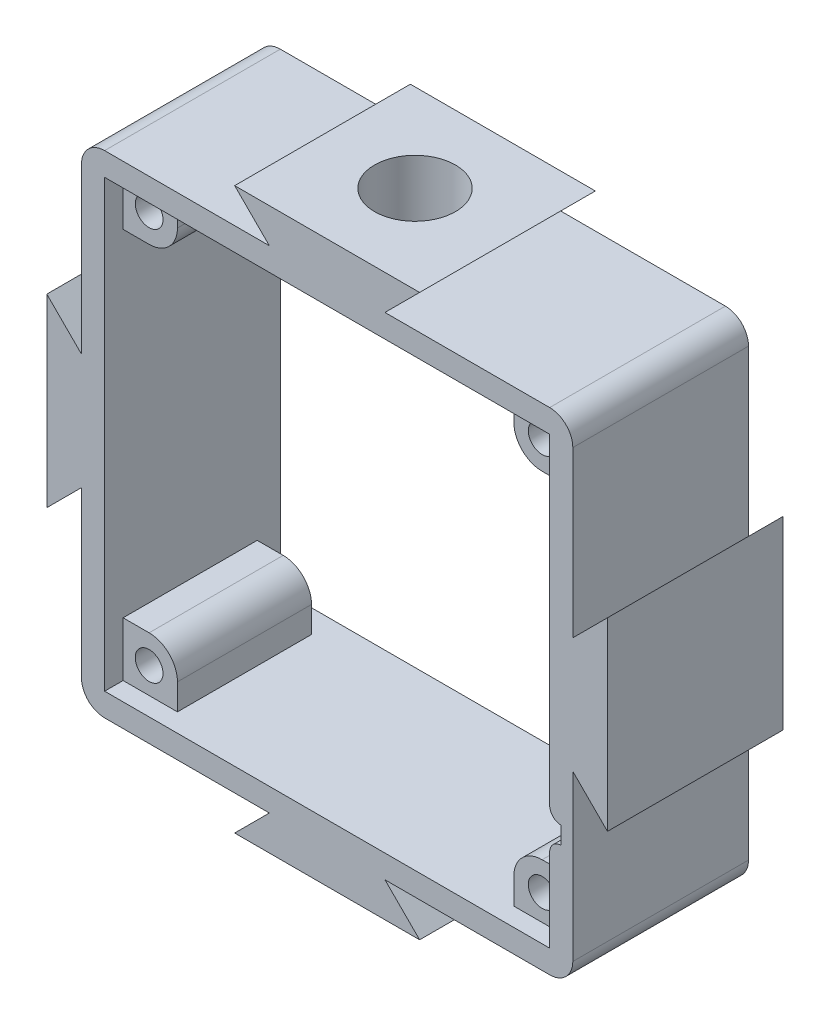
SolidWorks part; units mm, degrees
ref_plane "Front Plane" through (0, 0, 0) normal (0, 0, 1) x (1, 0, 0)
ref_plane "Top Plane" through (0, 0, 0) normal (0, 1, 0) x (1, 0, 0)
ref_plane "Right Plane" through (0, 0, 0) normal (1, 0, 0) x (0, 0, -1)
sketch "Sketch1" plane through (0, 0, 0) normal (0, 0, 1) x (1, 0, 0)
  line L0 (19.05, -19.05) -> (19.05, 19.05) construction
  line L5 (21.25, 21.25) -> (-21.25, 21.25)
  line L6 (-21.25, 21.25) -> (-21.25, -21.25)
  line L7 (-19.05, -19.05) -> (19.05, -19.05) construction
  line L8 (-19.05, 19.05) -> (-19.05, -19.05) construction
  line L9 (19.05, 19.05) -> (-19.05, 19.05) construction
  line L10 (19.05, -19.05) -> (19.05, 19.05) construction
  line L11 (-19.05, -19.05) -> (19.05, -19.05) construction
  line L12 (-19.05, 19.05) -> (-19.05, -19.05) construction
  line L13 (19.05, 19.05) -> (-19.05, 19.05) construction
  line L14 (19.25, -19.25) -> (19.25, 19.25)
  line L15 (19.25, 19.25) -> (-19.25, 19.25)
  line L16 (-19.25, 19.25) -> (-19.25, -19.25)
  line L17 (-19.25, -19.25) -> (19.25, -19.25)
  line L18 (-21.25, -21.25) -> (21.25, -21.25)
  line L19 (21.25, -21.25) -> (21.25, 21.25)
  point P17 (0, 0)
  point P18 (-25.4656, 13.9402)
  dimension "D2" = 2
  dimension "D1" = 0.2
extrude "Boss-Extrude2" add sketch "Sketch1" against normal up to surface (15.2 mm away)
sketch "Sketch2" plane through (0, 0, -1.6) normal (0, 0, -1) x (-1, 0, 0)
  line L0 (17, -14.55) -> (19.25, -14.55)
  line L1 (19.25, 19.25) -> (19.25, -19.25) construction
  line L2 (14.55, -17) -> (14.55, -19.25)
  line L3 (19.25, -19.25) -> (-19.25, -19.25) construction
  line L4 (19.25, -19.25) -> (14.55, -19.25)
  line L5 (19.25, -14.55) -> (19.25, -19.25)
  line L6 (19.05, -19.05) -> (-19.05, -19.05) construction
  line L7 (0, 0) -> (-50000, 0) construction
  line L8 (0, 0) -> (0, 50000) construction
  line L9 (19.25, 14.55) -> (19.25, 19.25)
  line L10 (19.25, 19.25) -> (14.55, 19.25)
  line L11 (14.55, 17) -> (14.55, 19.25)
  line L12 (17, 14.55) -> (19.25, 14.55)
  line L13 (-19.25, -14.55) -> (-19.25, -19.25)
  line L14 (-19.25, -19.25) -> (-14.55, -19.25)
  line L15 (-14.55, -17) -> (-14.55, -19.25)
  line L16 (-17, -14.55) -> (-19.25, -14.55)
  line L17 (-17, 14.55) -> (-19.25, 14.55)
  line L18 (-14.55, 17) -> (-14.55, 19.25)
  line L19 (-19.25, 19.25) -> (-14.55, 19.25)
  line L20 (-19.25, 14.55) -> (-19.25, 19.25)
  circle A2 centre (17, -17) radius 1.2 construction
  circle A3 centre (17, -17) radius 1.2
  arc A4 (17, -14.55) -> (14.55, -17) centre (17, -17) ccw
  arc A5 (17, 14.55) -> (14.55, 17) centre (17, 17) cw
  circle A6 centre (17, 17) radius 1.2
  arc A7 (-17, -14.55) -> (-14.55, -17) centre (-17, -17) cw
  circle A8 centre (-17, -17) radius 1.2
  circle A9 centre (-17, 17) radius 1.2
  arc A10 (-17, 14.55) -> (-14.55, 17) centre (-17, 17) ccw
  dimension "D1" = 4.5
extrude "Boss-Extrude4" add sketch "Sketch2" along normal offset from surface (11.6 mm away) 0.4 up to face at (0, 0, 0)
sketch "Sketch5" plane through (0, 0, 0) normal (0, 0, 1) x (1, 0, 0)
  line L0 (-21.25, 5) -> (-21.25, -5)
  line L1 (-21.25, 21.25) -> (-21.25, -21.25) construction
  line L2 (-21.25, -5) -> (-24.25, -8)
  line L3 (-24.25, -8) -> (-24.25, 8)
  line L4 (-24.25, 8) -> (-21.25, 5)
  point P5 (-24.25, 0)
  dimension "D1" = 45
  dimension "D2" = 45
  dimension "D3" = 10
  dimension "D4" = 3
extrude "Boss-Extrude5" add sketch "Sketch5" against normal up to surface (15.2 mm away) up to face at (0, 0, -15.2)
ref_axis "Axis1" through (0, 0, 0) along (0, 0, 1)
pattern_circular "CirPattern1" count 4 every 90 about axis through (0, 0, 0) along (0, 0, 1) of "Boss-Extrude5"
sketch "Sketch3" plane through (0, 0, 0) normal (0, 0, 1) x (1, 0, 0)
  line L0 (20.25, -11.05) -> (20.25, -9.55) construction
  line L1 (20.25, -11.05) -> (20.25, -9.55)
  line L2 (19.25, -8.55) -> (19.25, -12.05)
  arc A0 (19.25, -8.55) -> (20.25, -9.55) centre (20.25, -8.55) ccw construction
  arc A1 (20.25, -11.05) -> (19.25, -12.05) centre (20.25, -12.05) ccw construction
  arc A2 (19.25, -8.55) -> (20.25, -9.55) centre (20.25, -8.55) ccw
  arc A3 (20.25, -11.05) -> (19.25, -12.05) centre (20.25, -12.05) ccw
extrude "Cut-Extrude2" cut sketch "Sketch3" against normal blind 4
sketch "Sketch4" plane through (0, 24.25, 0) normal (0, 1, 0) x (1, 0, 0)
  line L1 (21.25, 0) -> (-21.25, 0) construction
  line L2 (21.25, 0) -> (21.25, 15.2) construction
  line L3 (21.25, 15.2) -> (-21.25, 15.2) construction
  line L4 (-21.25, 0) -> (-21.25, 15.2) construction
  line L5 (0, 15.2) -> (0, 0) construction
  line L6 (21.25, 7.6) -> (-21.25, 7.6) construction
  line L7 (21.25, 15.2) -> (5, 15.2) construction
  line L8 (21.25, 15.2) -> (21.25, 0) construction
  circle A0 centre (0, 7.6) radius 3.5
  point P6 (-19.25, 15.2)
  point P8 (-21.25, 15.2)
  point P9 (21.25, 0)
  point P11 (-19.25, 15.2)
  point P14 (21.25, 0)
  point P102 (0, 7.6)
  dimension "D1" = 7
extrude "Cut-Extrude3" cut sketch "Sketch4" against normal up to next
fillet "Fillet1" radius 2 4 edges at (21.25, 21.25, -7.6) (21.25, -21.25, -7.6) (-21.25, -21.25, -7.6) (-21.25, 21.25, -7.6)
